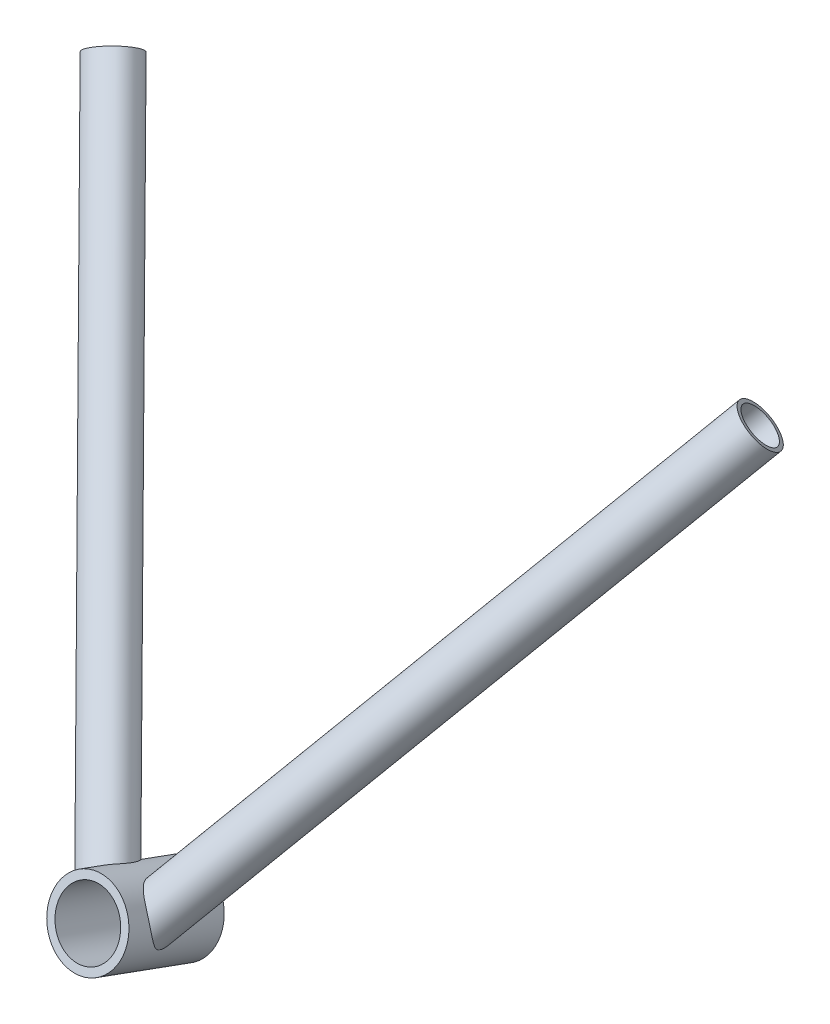
SolidWorks part; units mm, degrees
material "AISI 4130 Steel, normalized at 870C"
ref_plane "Front Plane" through (0, 0, 0) normal (0, 0, 1) x (1, 0, 0)
ref_plane "Top Plane" through (0, 0, 0) normal (0, 1, 0) x (1, 0, 0)
ref_plane "Right Plane" through (0, 0, 0) normal (1, 0, 0) x (0, 0, -1)
sketch "Sketch3" plane through (0, 0, 0) normal (0, 1, 0) x (1, 0, 0)
  line L0 (-5.08, -6.35) -> (5.08, -6.35) construction
  line L2 (0, -88.2205) -> (0, 88.2205) construction
  line L3 (5.08, 0) -> (-5.08, 0) construction
  dimension "D1" = 5.08
  dimension "D2" = 10.16
  dimension "D3" = 6.35
  dimension "D4" = 10.16
  dimension "D5" = 5.08
ref_plane "Plane1" through (0, 3.0196, 4.1561) normal (0, 0.5878, 0.809) x (1, 0, 0)
ref_plane "Plane3" through (0, 0, 0) normal (0, 0.342, 0.9397) x (-1, 0, 0)
sketch "Sketch1" plane through (0, 0, 0) normal (0, 0.342, 0.9397) x (1, 0, 0)
  circle A0 centre (0, 0) radius 15.875
  dimension "D1" = 31.75
extrude "Boss-Extrude1" add sketch "Sketch1" along normal mid plane 41.402 contours A0
sketch "Sketch4" plane through (0, 3.0196, 4.1561) normal (0, 0.5878, 0.809) x (1, 0, 0)
  line L0 (-5.08, -3.7324) -> (-132.08, 216.238)
  line L2 (0, -90.5202) -> (0, 90.5202) construction
  dimension "D2" = 30
  dimension "D3" = 254
sweep "Sweep1" add path "Sketch4" circular profile diameter 19.05 parameters "D3"=19.05
sketch "Sketch15" plane through (0, 3.0196, 4.1561) normal (0, 0.5878, 0.809) x (1, 0, 0)
  line L0 (5.08, -3.7324) -> (132.08, 216.238)
  line L1 (0, -90.5202) -> (0, 90.5202) construction
  dimension "D1" = 254
  dimension "D2" = 30
sweep "Sweep2" add path "Sketch15" circular profile diameter 19.05 parameters "D3"=19.05
sketch "Sketch36" plane through (-126.6538, 177.4747, -128.9429) normal (-0.5, 0.7006, -0.509) x (0.8656, 0.3849, -0.3204)
  circle A0 centre (-6.4316, -4.9279) radius 7.9375
  dimension "D1" = 15.875
extrude "Cut-Extrude2" cut sketch "Sketch36" against normal up to surface (272.4305 mm away) up to face at (14.6957, 3.6384, -7.5589)
sketch "Sketch37" plane through (126.6538, 177.4747, -128.9429) normal (0.5, 0.7006, -0.509) x (0.8656, -0.3849, 0.3204)
  circle A0 centre (6.4316, -4.9279) radius 7.9375
  dimension "D1" = 15.875
extrude "Cut-Extrude3" cut sketch "Sketch37" against normal up to surface (240.9848 mm away) up to face at (0.2372, -14.3112, 7.0906)
sketch "Sketch77" plane through (0, 7.0802, 19.4526) normal (0, 0.342, 0.9397) x (1, 0, 0)
  circle A1 centre (0, 0) radius 15.875
extrude "Boss-Extrude2" add sketch "Sketch77" against normal up to surface (41.402 mm away) up to face at (0, -21.9978, -14.023)
sketch "Sketch2" plane through (0, -7.0802, -19.4526) normal (0, -0.342, -0.9397) x (-1, 0, 0)
  circle A0 centre (0, 0) radius 12.7
  dimension "D1" = 25.4
extrude "Cut-Extrude1" cut sketch "Sketch2" against normal up to next
ref_plane "Plane2" through (0, 0, -127) normal (0, 0, 1) x (1, 0, 0)
ref_plane "Plane4" through (0, 177.8, 0) normal (0, 1, 0) x (1, 0, 0)
sketch "Sketch40" plane through (-106.934, 0, -127) normal (0, 0, 1) x (1, 0, 0)
  line L0 (108.4431, 184.15) -> (50108.4431, 184.15) construction
  line L1 (-45.466, 184.15) -> (259.334, 184.15)
  point P0 (106.934, 184.15)
  point P1 (106.934, 184.15)
  dimension "D1" = 304.8
  dimension "D5" = 184.15
sweep "Sweep5" [suppressed] add path "Sketch40" circular profile diameter 25.4 parameters "D3"=25.4
